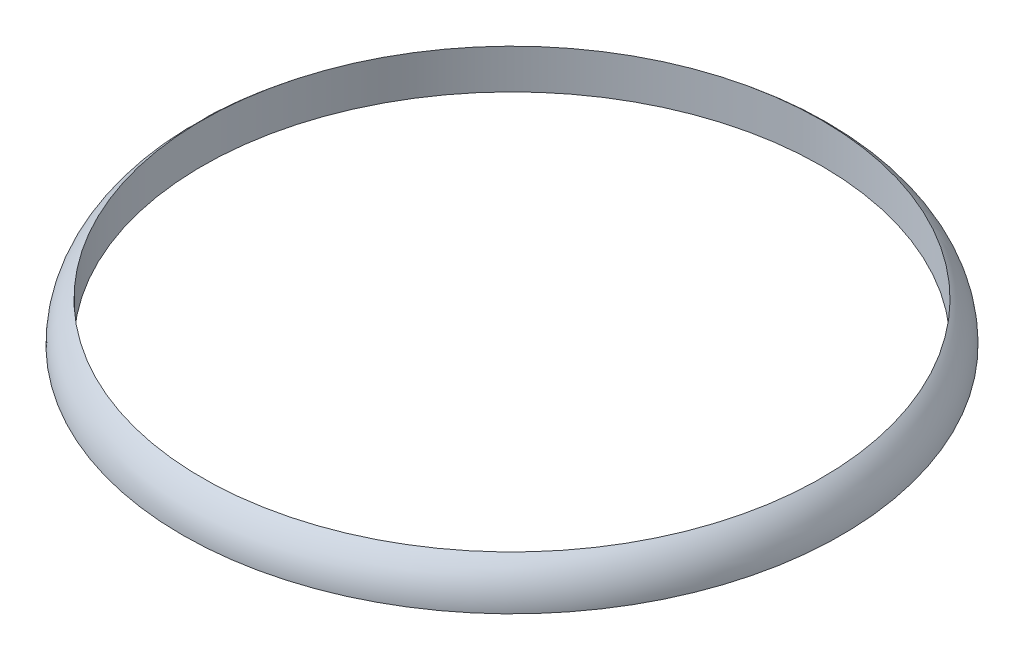
SolidWorks part; units mm, degrees
ref_plane "Front Plane" through (0, 0, 0) normal (0, 0, 1) x (1, 0, 0)
ref_plane "Top Plane" through (0, 0, 0) normal (0, 1, 0) x (1, 0, 0)
ref_plane "Right Plane" through (0, 0, 0) normal (1, 0, 0) x (0, 0, -1)
sketch "Sketch1" plane through (0, 0, 0) normal (1, 0, 0) x (0, 0, -1)
  line L0 (78.2, 0) -> (78.2, 10)
  line L1 (78.2, 0) -> (83.2, 0)
  line L2 (0, 0) -> (0, 45.7169) construction
  arc A1 (83.2, 0) -> (78.2, 10) centre (70.7, 0) ccw
  dimension "D1" = 5
  dimension "D2" = 10
  dimension "D3" = 78.2
revolve "Revolve1" add sketch "Sketch1" angle 360 about L2
